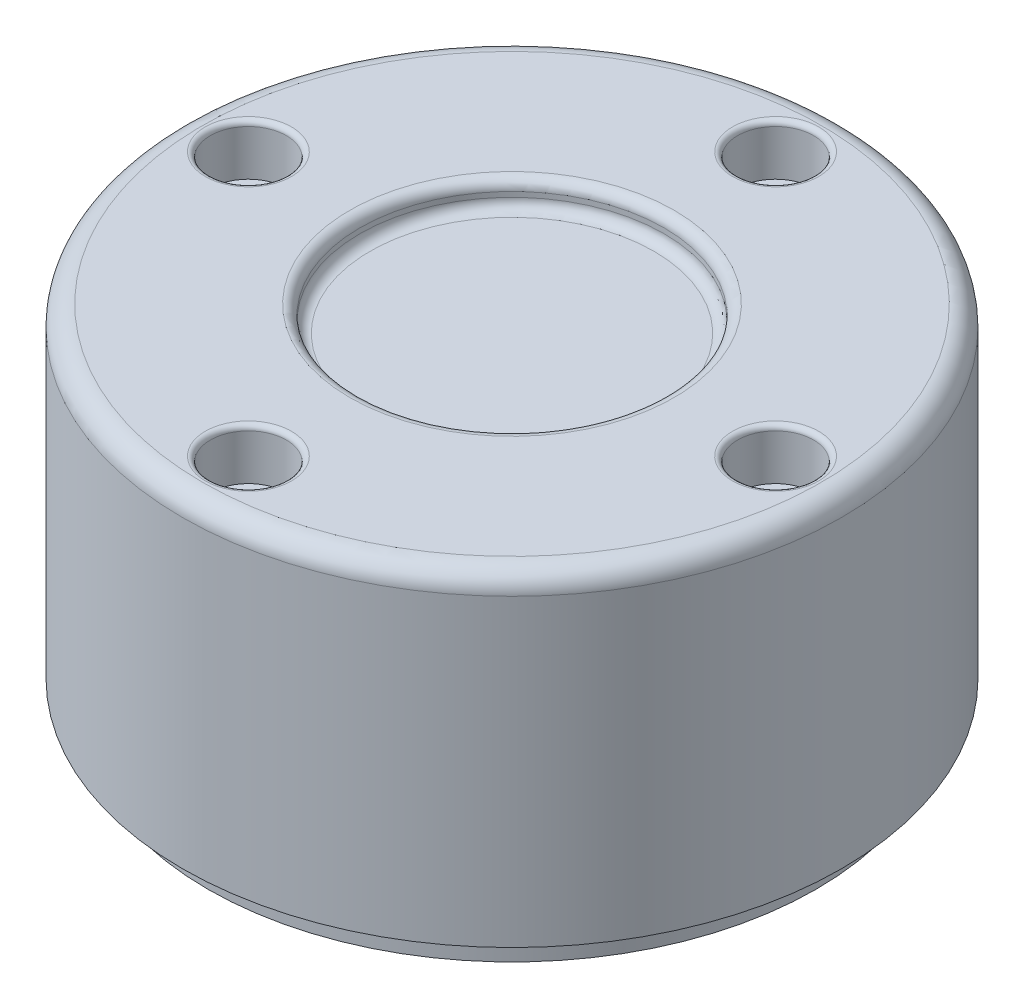
SolidWorks part; units mm, degrees
material "1060 Alloy"
ref_plane "Front Plane" through (0, 0, 0) normal (0, 0, 1) x (1, 0, 0)
ref_plane "Top Plane" through (0, 0, 0) normal (0, 1, 0) x (1, 0, 0)
ref_plane "Right Plane" through (0, 0, 0) normal (1, 0, 0) x (0, 0, -1)
sketch "Sketch2" plane through (0, 0, 0) normal (0, 1, 0) x (1, 0, 0)
  circle A0 centre (0, 0) radius 30
  dimension "D1" = 60
extrude "Boss-Extrude1" add sketch "Sketch2" along normal blind 3
sketch "Sketch3" plane through (0, 3, 0) normal (0, 1, 0) x (1, 0, 0)
  circle A0 centre (0, 0) radius 32.5
  dimension "D1" = 65
extrude "Boss-Extrude2" add sketch "Sketch3" along normal blind 32
sketch "Sketch4" plane through (0, 35, 0) normal (0, 1, 0) x (1, 0, 0)
  line L0 (0, 0) -> (0, 26) construction
  circle A0 centre (0, 0) radius 15
  circle A2 centre (0, 0) radius 32.5 construction
  circle A3 centre (0, 26) radius 3.75
  circle A4 centre (26, 0) radius 3.75
  circle A5 centre (0, -26) radius 3.75
  circle A6 centre (-26, 0) radius 3.75
  point P17 (0, 0)
  dimension "D1" = 30
  dimension "D2" = 26
  dimension "D3" = 7.5
  dimension "D4" = 4
extrude "Cut-Extrude1" cut sketch "Sketch4" against normal blind 2.5 contours A0
extrude "Cut-Extrude2" cut sketch "Sketch4<3>" against normal blind 5 contours A6 | A3 | A4 | A5 region at (0, 35, -26) region at (26, 35, 0) region at (-26, 35, 0)
sketch "Sketch4<3>" plane through (0, 35, 0) normal (0, 1, 0) x (1, 0, 0) same geometry as "Sketch4"
fillet "Fillet1" radius 1 1 edges at (0, 32.5, 15)
fillet "Fillet2" radius 1 1 edges at (0, 35, 15)
fillet "Fillet3" radius 2 1 edges at (0, 35, 32.5)
fillet "Fillet4" radius 0.5 4 edges at (0, 35, 29.75) (26, 35, 3.75) (0, 35, -22.25) (-26, 35, 3.75)
